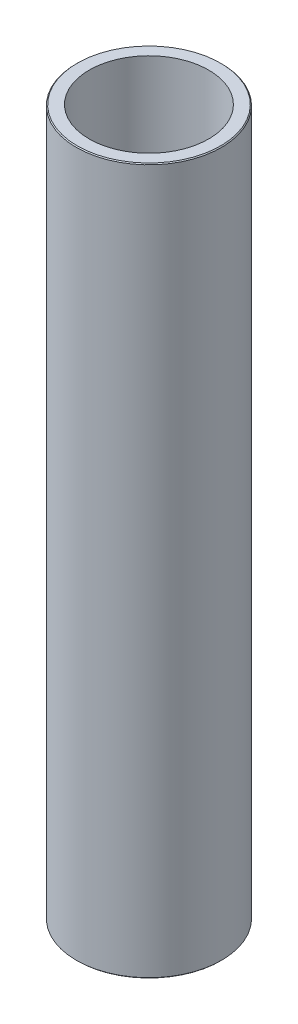
SolidWorks part; units mm, degrees
ref_plane "Front Plane" through (0, 0, 0) normal (0, 0, 1) x (1, 0, 0)
ref_plane "Top Plane" through (0, 0, 0) normal (0, 1, 0) x (1, 0, 0)
ref_plane "Right Plane" through (0, 0, 0) normal (1, 0, 0) x (0, 0, -1)
sketch "Sketch1" plane through (0, 0, 0) normal (0, 1, 0) x (1, 0, 0)
  circle A0 centre (0, 0) radius 57.5
  dimension "SHAFT_OD" = 115
extrude "Boss-Extrude1" add sketch "Sketch1" along normal blind 559.1953
sketch "Sketch2" plane through (0, 0, 0) normal (0, 1, 0) x (1, 0, 0)
  circle A0 centre (0, 0) radius 47.3326
  dimension "BORE_D" = 94.6652
extrude "Cut-Extrude1" cut sketch "Sketch2" along normal through all
chamfer "Chamfer1" distance 0.7218 angle 45 2 edges at (0, 559.1953, 57.5) (0, 0, 57.5)
